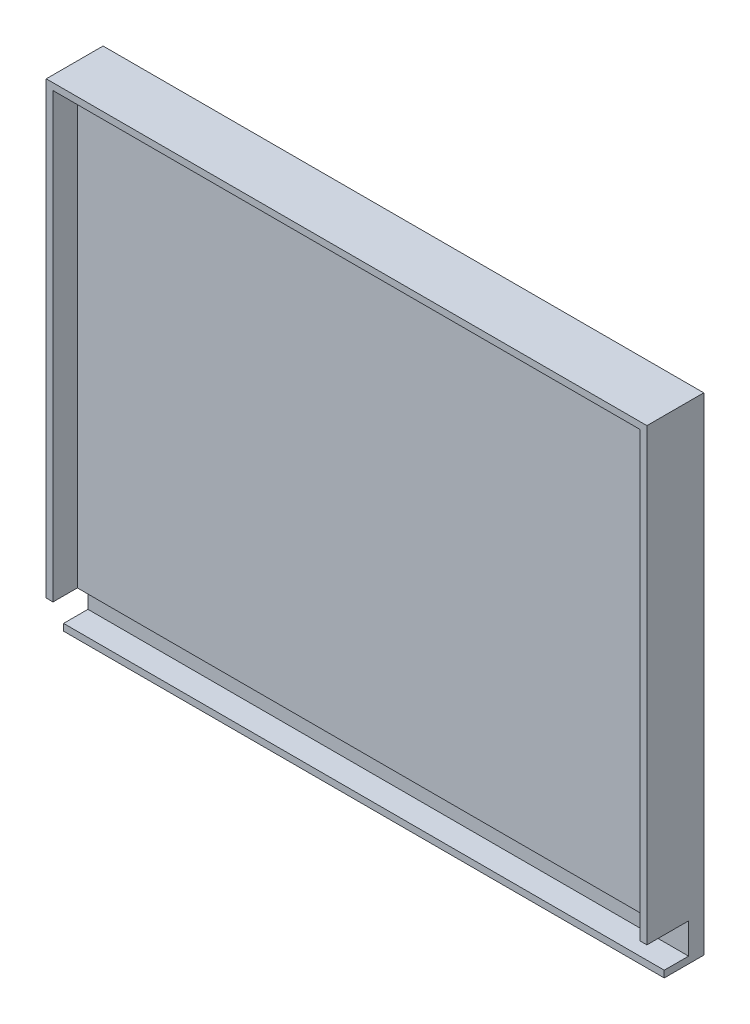
SolidWorks part; units mm, degrees
ref_plane "Front Plane" through (0, 0, 0) normal (0, 0, 1) x (1, 0, 0)
ref_plane "Top Plane" through (0, 0, 0) normal (0, 1, 0) x (1, 0, 0)
ref_plane "Right Plane" through (0, 0, 0) normal (1, 0, 0) x (0, 0, -1)
sketch "Sketch1" plane through (0, 0, 0) normal (0, 0, 1) x (1, 0, 0)
  line L1 (-68.3632, 130.6396) -> (213.5768, 130.6396)
  line L2 (-68.3632, 130.6396) -> (-68.3632, -97.9604)
  line L3 (-68.3632, -97.9604) -> (213.5768, -97.9604)
  line L4 (213.5768, 130.6396) -> (213.5768, -97.9604)
  dimension "D1" = 281.94
  dimension "D2" = 228.6
extrude "Boss-Extrude2" add sketch "Sketch1" along normal blind 25.4
sketch "Sketch3" plane through (0, 0, 25.4) normal (0, 0, 1) x (1, 0, 0)
  line L0 (-68.3632, -97.9604) -> (-68.3632, -80.4344)
  line L1 (-68.3632, 130.6396) -> (-68.3632, -97.9604) construction
  line L2 (-68.3632, -80.4344) -> (213.5768, -80.4344)
  line L3 (213.5768, -97.9604) -> (213.5768, 130.6396) construction
  line L4 (213.5768, -80.4344) -> (213.5768, -97.9604)
  line L5 (213.5768, -97.9604) -> (-68.3632, -97.9604)
  dimension "D1" = 17.526
extrude "Cut-Extrude1" cut sketch "Sketch3" against normal blind 8.128
sketch "Sketch4" plane through (-68.3632, 0, 0) normal (-1, 0, 0) x (0, 0, 1)
  line L0 (25.4, 130.6396) -> (36.83, 130.6396)
  line L1 (36.83, 130.6396) -> (36.83, -80.4344)
  line L2 (36.83, -80.4344) -> (25.4, -80.4344)
  line L3 (25.4, -80.4344) -> (25.4, 130.6396)
  dimension "D1" = 11.43
extrude "Boss-Extrude4" add sketch "Sketch4" against normal blind 3.175 separate body
sketch "Sketch5" plane through (0, 130.6396, 0) normal (0, 1, 0) x (1, 0, 0)
  line L15 (-65.1882, -36.83) -> (-65.1882, -25.4)
  line L16 (-65.1882, -25.4) -> (213.5768, -25.4)
  line L17 (213.5768, -25.4) -> (213.5768, -36.83)
  line L18 (213.5768, -36.83) -> (-65.1882, -36.83)
sketch "Sketch8" plane through (0, -97.9604, 0) normal (0, -1, 0) x (1, 0, 0)
  line L0 (-68.3632, 17.272) -> (-68.3632, 28.702)
  line L1 (-68.3632, 28.702) -> (213.5768, 28.702)
  line L2 (213.5768, 28.702) -> (213.5768, 17.272)
  line L3 (213.5768, 17.272) -> (-68.3632, 17.272)
  dimension "D1" = 11.43
extrude "Boss-Extrude9" add sketch "Sketch5" against normal blind 3.175
sketch "Sketch9" plane through (213.5768, 0, 0) normal (1, 0, 0) x (0, 0, -1)
  line L0 (-25.4, -80.4344) -> (-36.83, -80.4344)
  line L1 (-36.83, -80.4344) -> (-36.83, 127.4646)
  line L2 (-36.83, 127.4646) -> (-25.4, 127.4646)
  line L3 (-25.4, 127.4646) -> (-25.4, -80.4344)
  dimension "D1" = 11.43
extrude "Boss-Extrude10" add sketch "Sketch9" against normal blind 3.175
extrude "Boss-Extrude11" add sketch "Sketch8" against normal blind 3.175 separate body
combine bodies "Combine1" operation type add bodies to combine 115 114
sketch "Sketch10" plane through (0, 0, 17.272) normal (0, 0, 1) x (1, 0, 0)
  line L0 (213.5768, -80.4344) -> (213.5768, -94.7854)
  line L1 (213.5768, -94.7854) -> (-68.3632, -94.7854)
  line L2 (-68.3632, -94.7854) -> (-68.3632, -80.4344)
  line L3 (-68.3632, -80.4344) -> (213.5768, -80.4344)
extrude "Cut-Extrude2" cut sketch "Sketch10" against normal blind 10.16
sketch "Sketch11" plane through (0, 0, 25.4) normal (0, 0, 1) x (1, 0, 0)
  line L0 (210.4018, 127.4646) -> (210.4018, -80.4344)
  line L1 (210.4018, -80.4344) -> (-65.1882, -80.4344)
  line L2 (-65.1882, -80.4344) -> (-65.1882, 127.4646)
  line L3 (-65.1882, 127.4646) -> (210.4018, 127.4646)
extrude "Cut-Extrude3" cut sketch "Sketch11" against normal blind 10.16
sketch "Sketch12" plane through (0, 0, 36.83) normal (0, 0, 1) x (1, 0, 0)
  line L0 (-68.3632, -80.4344) -> (-65.1882, -80.4344)
  line L1 (-65.1882, -80.4344) -> (-65.1882, 127.4646)
  line L2 (-65.1882, 127.4646) -> (210.4018, 127.4646)
  line L3 (210.4018, 127.4646) -> (210.4018, -80.4344)
  line L4 (210.4018, -80.4344) -> (213.5768, -80.4344)
  line L5 (213.5768, -80.4344) -> (213.5768, 130.6396)
  line L6 (213.5768, 130.6396) -> (-68.3632, 130.6396)
  line L7 (-68.3632, 130.6396) -> (-68.3632, -80.4344)
extrude "Cut-Extrude4" cut sketch "Sketch12" against normal blind 10.16
sketch "Sketch13" plane through (0, 0, 28.702) normal (0, 0, 1) x (1, 0, 0)
  line L0 (-68.3632, -94.7854) -> (-68.3632, -97.9604)
  line L1 (-68.3632, -97.9604) -> (213.5768, -97.9604)
  line L2 (213.5768, -97.9604) -> (213.5768, -94.7854)
  line L3 (213.5768, -94.7854) -> (-68.3632, -94.7854)
extrude "Cut-Extrude5" cut sketch "Sketch13" against normal blind 10.16
shell "Shell4" thickness 2.54
